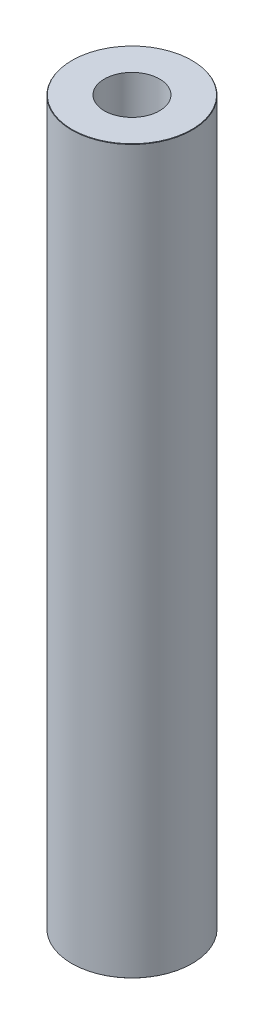
SolidWorks part; units mm, degrees
ref_plane "Front Plane" through (0, 0, 0) normal (0, 0, 1) x (1, 0, 0)
ref_plane "Top Plane" through (0, 0, 0) normal (0, 1, 0) x (1, 0, 0)
ref_plane "Right Plane" through (0, 0, 0) normal (1, 0, 0) x (0, 0, -1)
sketch "Sketch1" plane through (0, 0, 0) normal (0, 1, 0) x (1, 0, 0)
  circle A0 centre (0, 0) radius 50
  dimension "SHAFT_OD" = 100
extrude "Boss-Extrude1" add sketch "Sketch1" along normal blind 600
sketch "Sketch2" plane through (0, 0, 0) normal (0, 1, 0) x (1, 0, 0)
  circle A0 centre (0, 0) radius 22.9211
  dimension "BORE_D" = 45.8422
extrude "Cut-Extrude1" cut sketch "Sketch2" along normal through all
chamfer "Chamfer1" distance 0.3272 angle 39.79 2 edges at (0, 600, 50) (0, 0, 50) first distance on face at (0, 600, 50) first distance on face at (0, 0, 22.9211)
